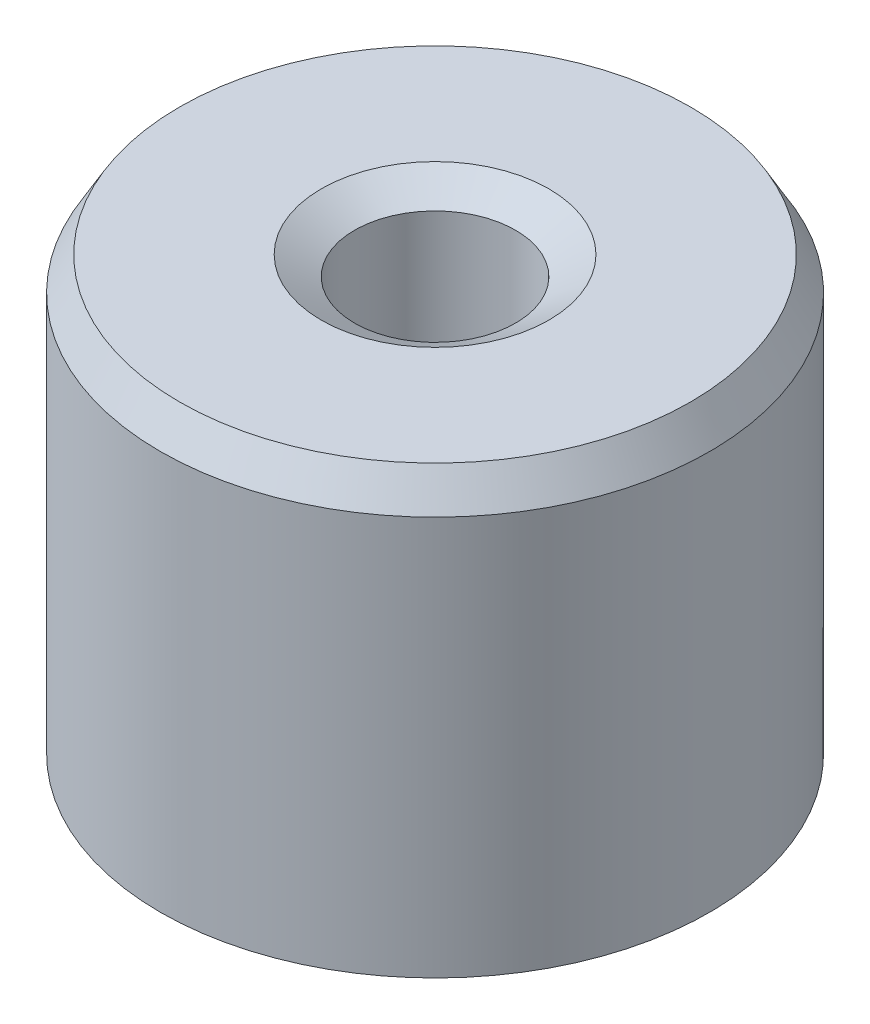
SolidWorks part; units mm, degrees
ref_plane "Front Plane" through (0, 0, 0) normal (0, 0, 1) x (1, 0, 0)
ref_plane "Top Plane" through (0, 0, 0) normal (0, 1, 0) x (1, 0, 0)
ref_plane "Right Plane" through (0, 0, 0) normal (1, 0, 0) x (0, 0, -1)
sketch "Sketch1" plane through (0, 0, 0) normal (0, 1, 0) x (1, 0, 0)
  circle A0 centre (0, 0) radius 5
  dimension "SLEEVE_OD" = 10
extrude "Boss-Extrude1" add sketch "Sketch1" along normal blind 8.2185
sketch "Sketch2" plane through (0, 0, 0) normal (0, 1, 0) x (1, 0, 0)
  circle A0 centre (0, 0) radius 1.4655
  dimension "BORE_D" = 2.9309
extrude "Cut-Extrude1" cut sketch "Sketch2" along normal through all
chamfer "Chamfer1" distance 0.6056 angle 30 4 edges at (0, 8.2185, 1.4655) (0, 0, 1.4655) (0, 0, 5) (0, 8.2185, 5) first distance on face at (0, 8.2185, 1.4655) first distance on face at (0, 0, 1.4655) first distance on face at (0, 8.2185, 5)
